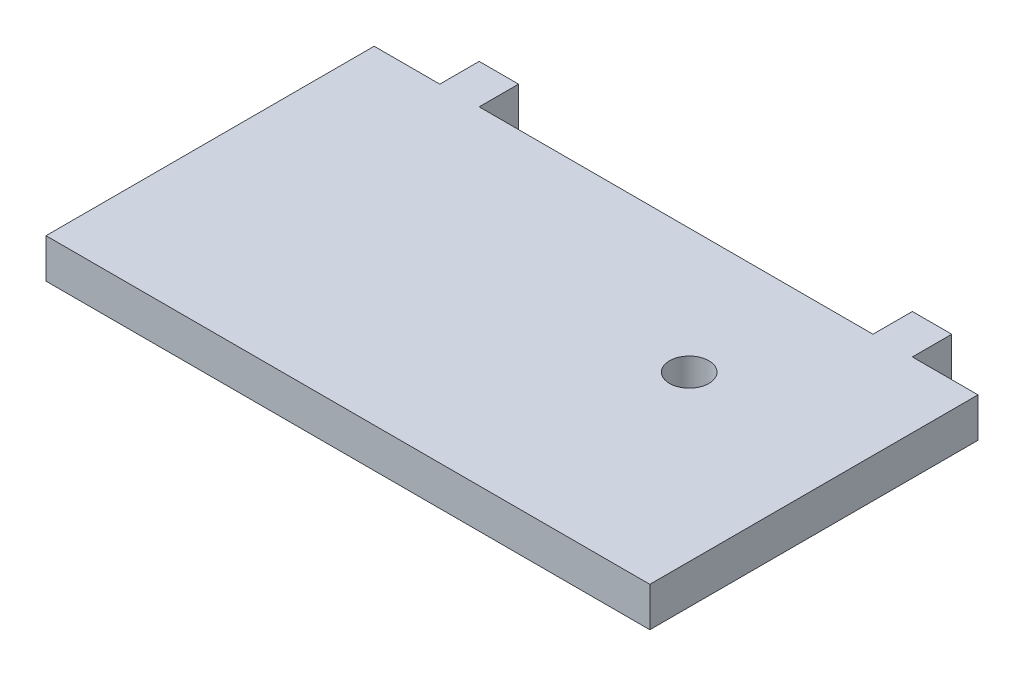
SolidWorks part; units mm, degrees
material "Pine"
ref_plane "정면" through (0, 0, 0) normal (0, 0, 1) x (1, 0, 0)
ref_plane "윗면" through (0, 0, 0) normal (0, 1, 0) x (1, 0, 0)
ref_plane "우측면" through (0, 0, 0) normal (1, 0, 0) x (0, 0, -1)
sketch "Sketch1" plane through (0, 0, 0) normal (0, 0, 1) x (1, 0, 0)
  line L0 (0, -18.5254) -> (0, 26.4304) construction
  line L1 (-46, 0) -> (46, 0)
  line L2 (-46, 0) -> (-46, 6)
  line L3 (-46, 6) -> (46, 6)
  line L4 (46, 6) -> (46, 0)
  dimension "D1" = 92
  dimension "D2" = 6
  dimension "D3" = 46
extrude "Boss-Extrude1" add sketch "Sketch1" along normal blind 50
sketch "Sketch2" plane through (0, 0, 0) normal (0, 0, -1) x (-1, 0, 0)
  line L0 (-36, 0) -> (-36, 6)
  line L1 (46, 0) -> (-46, 0) construction
  line L2 (-46, 6) -> (46, 6) construction
  line L3 (-36, 6) -> (-30, 6)
  line L4 (-30, 6) -> (-30, 0)
  line L5 (-30, 0) -> (-36, 0)
  line L6 (-46, 0) -> (-46, 6) construction
  line L7 (0, -3.4113) -> (0, 11.4135) construction
  line L8 (30, 0) -> (36, 0)
  line L9 (30, 6) -> (30, 0)
  line L10 (36, 6) -> (30, 6)
  line L11 (36, 0) -> (36, 6)
  line L12 (46, 6) -> (46, 0) construction
  dimension "D1" = 6
  dimension "D2" = 6
  dimension "D3" = 10
  dimension "D4" = 10
extrude "Boss-Extrude2" add sketch "Sketch2" along normal blind 6
sketch "Sketch3" plane through (0, 0, 0) normal (0, -1, 0) x (1, 0, 0)
  line L0 (46, 50) -> (46, 0) construction
  line L1 (-30, 0) -> (30, 0) construction
  circle A0 centre (21, 19) radius 3
  dimension "D1" = 25
  dimension "D2" = 19
extrude "Cut-Extrude1" cut sketch "Sketch3" against normal blind 6 contours A0
